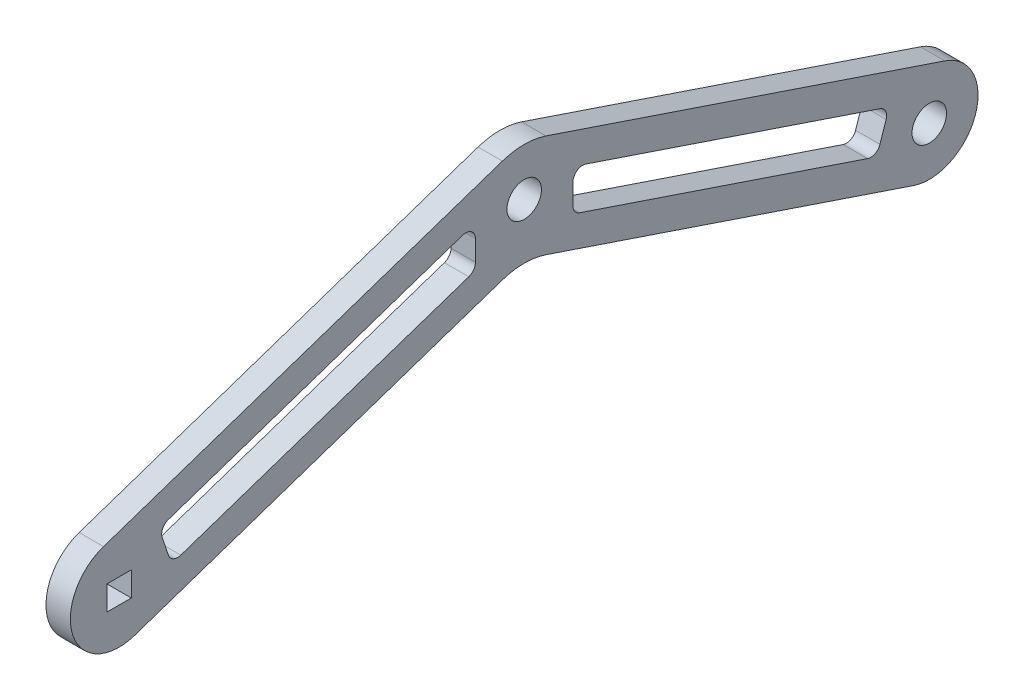
SolidWorks part; units mm, degrees
material "Custom Plastic"
ref_plane "Front Plane" through (0, 0, 0) normal (0, 0, 1) x (1, 0, 0)
ref_plane "Top Plane" through (0, 0, 0) normal (0, 1, 0) x (1, 0, 0)
ref_plane "Right Plane" through (0, 0, 0) normal (1, 0, 0) x (0, 0, -1)
sketch "Sketch1" plane through (0, 0, 0) normal (1, 0, 0) x (0, 0, -1)
  line L0 (0, 0) -> (-105.5116, 0) construction
  line L1 (-105.5116, 0) -> (-52.7558, 17.78) construction
  line L2 (-103.9241, -1.5875) -> (-107.0991, -1.5875)
  line L3 (-103.9241, -1.5875) -> (-103.9241, 1.5875)
  line L4 (-103.9241, 1.5875) -> (-107.0991, 1.5875)
  line L5 (-107.0991, -1.5875) -> (-107.0991, 1.5875)
  line L6 (-103.9241, -1.5875) -> (-107.0991, 1.5875) construction
  line L7 (-103.9241, 1.5875) -> (-107.0991, -1.5875) construction
  line L8 (1.5875, -1.5875) -> (-1.5875, -1.5875) construction
  line L9 (1.5875, -1.5875) -> (1.5875, 1.5875) construction
  line L10 (1.5875, 1.5875) -> (-1.5875, 1.5875) construction
  line L11 (-1.5875, -1.5875) -> (-1.5875, 1.5875) construction
  line L12 (1.5875, -1.5875) -> (-1.5875, 1.5875) construction
  line L13 (1.5875, 1.5875) -> (-1.5875, -1.5875) construction
  line L14 (-52.7558, 17.78) -> (0, 0) construction
  line L15 (-107.5396, 6.0174) -> (-55.595, 23.524)
  line L16 (-49.9166, 23.524) -> (2.028, 6.0174)
  line L17 (2.028, 6.0174) -> (-2.028, -6.0174) construction
  line L18 (-2.028, -6.0174) -> (-49.9166, 10.1222)
  line L19 (-55.595, 10.1222) -> (-103.4836, -6.0174)
  line L20 (-107.5396, 6.0174) -> (-103.4836, -6.0174) construction
  line L21 (-99.8998, 3.2315) -> (-99.0886, 0.8245)
  line L22 (-97.4795, 0.0267) -> (-59.9702, 12.6682)
  line L23 (-45.5414, 12.6682) -> (-8.0321, 0.0267)
  line L24 (-6.423, 0.8245) -> (-5.6118, 3.2315)
  line L25 (-6.4097, 4.8406) -> (-44.7302, 17.7555)
  line L26 (-60.7814, 17.7555) -> (-99.1019, 4.8406)
  line L27 (-52.7558, 20.4604) -> (-52.7558, 17.78) construction
  line L28 (-52.7558, 17.78) -> (-52.7558, 15.0996) construction
  line L29 (-59.1058, 16.5521) -> (-59.1058, 13.8717)
  line L30 (-59.1058, 12.9595) -> (-52.7558, 15.0996) construction
  line L31 (-46.4058, 13.8717) -> (-46.4058, 16.5521)
  line L32 (-52.7558, 15.0996) -> (-46.4058, 12.9595) construction
  line L33 (-59.1058, 18.3203) -> (-52.7558, 20.4604) construction
  line L34 (-52.7558, 20.4604) -> (-46.4058, 18.3203) construction
  line L35 (-59.1058, 17.78) -> (-52.7558, 17.78) construction
  line L36 (-52.7558, 17.78) -> (-46.4058, 17.78) construction
  circle A0 centre (0, 0) radius 2.2451
  arc A1 (-107.5396, 6.0174) -> (-103.4836, -6.0174) centre (-105.5116, 0) ccw
  arc A2 (2.028, 6.0174) -> (-2.028, -6.0174) centre (0, 0) cw
  arc A3 (-49.9166, 10.1222) -> (-55.595, 10.1222) centre (-52.7558, 1.6978) ccw
  arc A4 (-55.595, 23.524) -> (-49.9166, 23.524) centre (-52.7558, 15.0996) cw
  arc A5 (-99.8998, 3.2315) -> (-99.1019, 4.8406) centre (-98.6963, 3.6371) cw
  arc A6 (-99.0886, 0.8245) -> (-97.4795, 0.0267) centre (-97.8851, 1.2301) ccw
  arc A7 (-8.0321, 0.0267) -> (-6.423, 0.8245) centre (-7.6265, 1.2301) ccw
  arc A8 (-5.6118, 3.2315) -> (-6.4097, 4.8406) centre (-6.8153, 3.6371) ccw
  arc A9 (-46.4058, 16.5521) -> (-44.7302, 17.7555) centre (-45.1358, 16.5521) cw
  arc A10 (-45.5414, 12.6682) -> (-46.4058, 13.8717) centre (-45.1358, 13.8717) cw
  arc A11 (-59.1058, 13.8717) -> (-59.9702, 12.6682) centre (-60.3758, 13.8717) cw
  arc A12 (-59.1058, 16.5521) -> (-60.7814, 17.7555) centre (-60.3758, 16.5521) ccw
  circle A13 centre (-52.7558, 17.78) radius 2.2451
  dimension "D6" = 6.35
  dimension "D5" = 8.89
  dimension "D7" = 1.27
  dimension "D1" = 105.5116
  dimension "D2" = 3.175
  dimension "D3" = 17.78
  dimension "D4" = 6.35
  dimension "D8" = 6.35
extrude "Boss-Extrude1" add sketch "Sketch1" along normal blind 3.175
